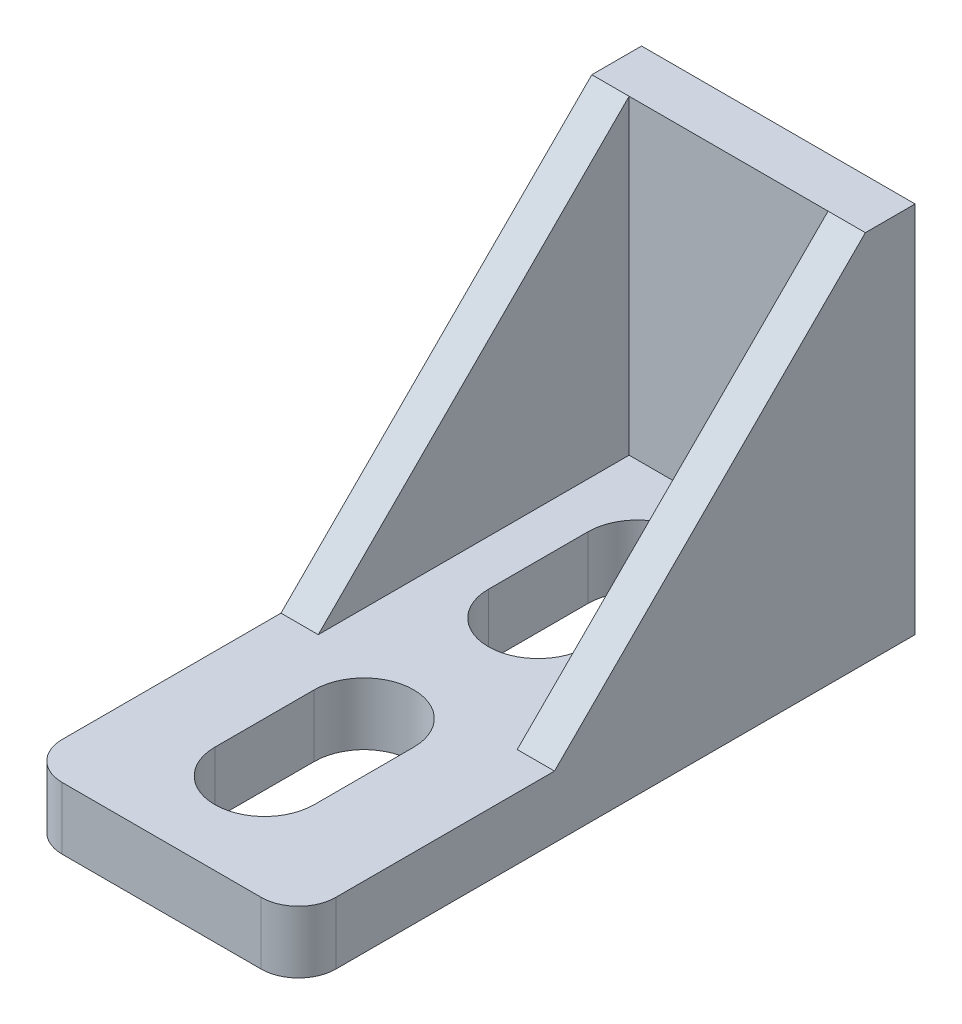
SolidWorks part; units mm, degrees
ref_plane "Front Plane" through (0, 0, 0) normal (0, 0, 1) x (1, 0, 0)
ref_plane "Top Plane" through (0, 0, 0) normal (0, 1, 0) x (1, 0, 0)
ref_plane "Right Plane" through (0, 0, 0) normal (1, 0, 0) x (0, 0, -1)
sketch "Sketch1" plane through (0, 0, 0) normal (0, 1, 0) x (1, 0, 0)
  line L0 (-4.0482, -4.7204) -> (-4.0482, 3.2796)
  line L1 (3.9518, -4.7204) -> (3.9518, 3.2796)
  line L2 (-4.0482, -26.7204) -> (-4.0482, -18.7204)
  line L3 (3.9518, -26.7204) -> (3.9518, -18.7204)
  line L4 (-0.0482, 3.2796) -> (0.2762, 14.2796) construction
  line L5 (0.2762, 14.2796) -> (11.2762, 14.2796)
  line L6 (11.2762, 14.2796) -> (11.2762, -35.3102)
  line L7 (11.2762, -35.3102) -> (-10.7238, -35.3102)
  line L8 (-10.7238, -35.3102) -> (-10.7238, 14.2796)
  line L9 (-10.7238, 14.2796) -> (0.2762, 14.2796)
  arc A0 (-4.0482, 3.2796) -> (3.9518, 3.2796) centre (-0.0482, 3.2796) cw
  arc A1 (-4.0482, -4.7204) -> (3.9518, -4.7204) centre (-0.0482, -4.7204) ccw
  arc A2 (-4.0482, -18.7204) -> (3.9518, -18.7204) centre (-0.0482, -18.7204) cw
  arc A3 (-4.0482, -26.7204) -> (3.9518, -26.7204) centre (-0.0482, -26.7204) ccw
  dimension "D1" = 4
  dimension "D2" = 22
  dimension "D3" = 8
  dimension "D4" = 8
  dimension "D5" = 11
  dimension "D6" = 22
extrude "Boss-Extrude1" add sketch "Sketch1" along normal blind 5
sketch "Sketch2" plane through (0, 0, 0) normal (0, 1, 0) x (1, 0, 0)
  line L0 (-10.7238, 14.2796) -> (-10.7238, -35.3102) construction
  line L1 (-10.7238, 14.2796) -> (11.2762, 14.2796)
  line L2 (-10.7238, 14.2796) -> (-10.7238, 10.2796)
  line L3 (-10.7238, 10.2796) -> (11.2762, 10.2796)
  line L4 (11.2762, 14.2796) -> (11.2762, 10.2796)
  line L5 (11.2762, -35.3102) -> (11.2762, 14.2796) construction
  line L6 (11.2762, 14.2796) -> (-10.7238, 14.2796) construction
  dimension "D1" = 4
extrude "Boss-Extrude2" add sketch "Sketch2" along normal blind 30
sketch "Sketch6" plane through (0, 0, 0) normal (1, 0, 0) x (0, 0, -1)
  line L0 (10.2796, 30) -> (10.2796, 5)
  line L1 (10.2796, 5) -> (-14.7204, 5)
  line L2 (-14.7204, 5) -> (10.2796, 30)
  line L3 (10.2796, 30) -> (10.2796, 5) construction
  line L4 (10.2796, 5) -> (-35.3102, 5) construction
extrude "Boss-Extrude3" add sketch "Sketch6" along normal blind 3 from surface starting at face at (-10.7238, 11.6667, 3.5837)
extrude "Boss-Extrude4" add sketch "Sketch6<2>" against normal blind 3 from surface starting at face at (11.2762, 11.6667, 3.5837)
sketch "Sketch6<2>" plane through (0, 0, 0) normal (1, 0, 0) x (0, 0, -1) same geometry as "Sketch6"
fillet "Fillet1" radius 3 2 edges at (11.2762, 2.5, 35.3102) (-10.7238, 2.5, 35.3102)
